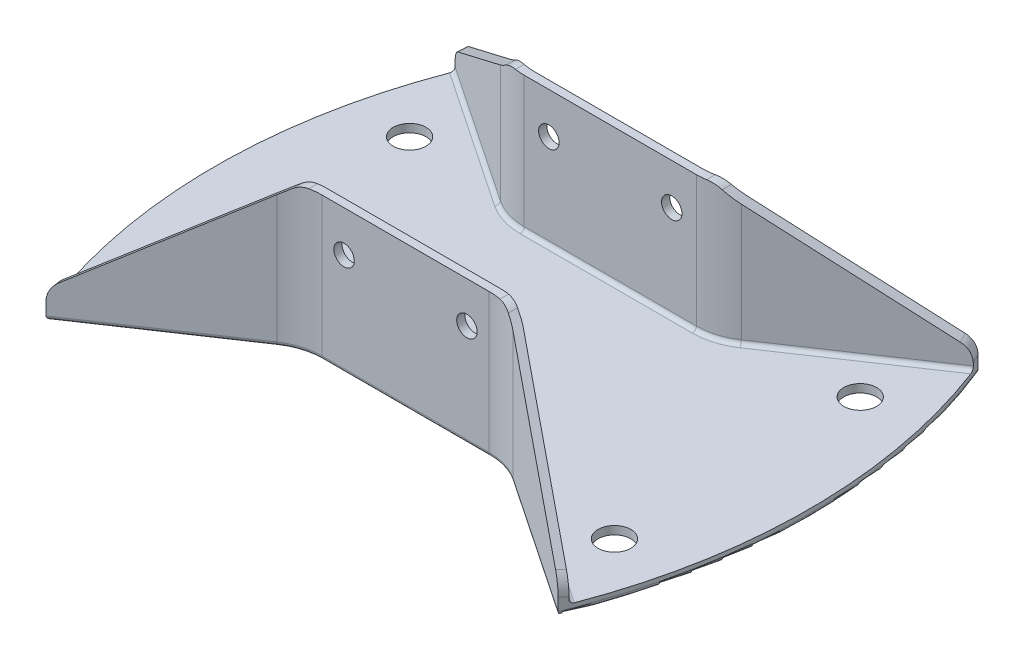
SolidWorks part; units mm, degrees
ref_plane "Front Plane" through (0, 0, 0) normal (0, 0, 1) x (1, 0, 0)
ref_plane "Top Plane" through (0, 0, 0) normal (0, 1, 0) x (1, 0, 0)
ref_plane "Right Plane" through (0, 0, 0) normal (1, 0, 0) x (0, 0, -1)
sketch "Sketch1" plane through (0, 0, 0) normal (0, 1, 0) x (1, 0, 0)
  line L1 (-72.5, 51.25) -> (72.5, 51.25)
  line L2 (-72.5, 51.25) -> (-72.5, -51.25)
  line L3 (-72.5, -51.25) -> (72.5, -51.25)
  line L4 (72.5, 51.25) -> (72.5, -51.25)
  line L5 (-72.5, 51.25) -> (72.5, -51.25) construction
  line L6 (-72.5, -51.25) -> (72.5, 51.25) construction
  point P0 (0, 0)
  dimension "D1" = 145
  dimension "D2" = 102.5
extrude "Boss-Extrude1" add sketch "Sketch1" along normal blind 35
sketch "Sketch2" plane through (0, 35, 0) normal (0, 1, 0) x (1, 0, 0)
  line L0 (-62.5, 51.25) -> (-62.5, -51.25) construction
  line L1 (-25, 26) -> (25, 26)
  line L3 (-25, -26) -> (25, -26)
  line L5 (-25, 26) -> (25, -26) construction
  line L6 (-25, -26) -> (25, 26) construction
  line L7 (72.5, 51.25) -> (-72.5, 51.25) construction
  line L8 (-72.5, -51.25) -> (72.5, -51.25) construction
  line L9 (62.5, 51.25) -> (62.5, -51.25) construction
  line L10 (-72.5, 51.25) -> (-72.5, -51.25) construction
  line L11 (72.5, -51.25) -> (72.5, 51.25) construction
  line L12 (-62.5, 51.25) -> (-25, 26)
  line L13 (62.5, 51.25) -> (25, 26)
  line L14 (-62.5, -51.25) -> (-25, -26)
  line L15 (25, -26) -> (62.5, -51.25)
  arc A0 (-62.5, 51.25) -> (-62.5, -51.25) centre (63.8281, 0) ccw
  arc A1 (62.5, 51.25) -> (62.5, -51.25) centre (-63.8281, 0) cw
  point P0 (0, 0)
  dimension "D1" = 52
  dimension "D2" = 50
  dimension "D3" = 10
  dimension "D4" = 10
  dimension "D5" = 25
  dimension "D6" = 26
extrude "Cut-Extrude1" cut sketch "Sketch2" against normal blind 35 flip side to cut
sketch "Sketch3" plane through (0, 35, 0) normal (0, 1, 0) x (1, 0, 0)
  line L6 (-80, 60.6222) -> (-80, -60.6222)
  line L7 (80, 60.6222) -> (80, -60.6222)
  line L12 (-61.5538, -48.2018) -> (-25.6106, -24)
  line L13 (-25.6106, -24) -> (25.6106, -24)
  line L14 (25.6106, -24) -> (61.5538, -48.2018)
  line L15 (61.5538, 48.2018) -> (25.6106, 24)
  line L16 (25.6106, 24) -> (-25.6106, 24)
  line L17 (-25.6106, 24) -> (-61.5538, 48.2018)
  line L18 (-80, -60.6222) -> (-25.6106, -24)
  line L19 (-25.6106, -24) -> (25.6106, -24)
  line L20 (25.6106, -24) -> (80, -60.6222)
  line L21 (80, 60.6222) -> (25.6106, 24)
  line L22 (25.6106, 24) -> (-25.6106, 24)
  line L23 (-25.6106, 24) -> (-80, 60.6222)
  arc A4 (61.5538, -48.2018) -> (61.5538, 48.2018) centre (-63.8281, 0) ccw
  arc A5 (-61.5538, 48.2018) -> (-61.5538, -48.2018) centre (63.8281, 0) ccw
  dimension "D2" = 80
  dimension "D3" = 80
  dimension "D1" = 2
extrude "Cut-Extrude2" cut sketch "Sketch3" against normal blind 33
sketch "Sketch6" plane through (0, 0, 0) normal (0, 0, 1) x (1, 0, 0)
  line L0 (-65, 5) -> (-25, 35)
  line L1 (-25, 35) -> (25, 35)
  line L2 (25, 35) -> (65, 5)
  line L3 (65, 5) -> (65, 40)
  line L4 (65, 40) -> (-65, 40)
  line L5 (-65, 40) -> (-65, 5)
  circle A0 centre (-15, 25) radius 2.5
  circle A1 centre (15, 25) radius 2.5
  dimension "D7" = 5
  dimension "D8" = 5
  dimension "D1" = 5
  dimension "D2" = 5
  dimension "D3" = 130
  dimension "D4" = 65
  dimension "D5" = 40
  dimension "D6" = 25
  dimension "D9" = 15
  dimension "D10" = 30
extrude "Cut-Extrude6" cut sketch "Sketch6" against normal through all both and the other way through all
fillet "Fillet1" radius 5 8 edges at (62.8812, 6.5891, -50.3001) (62.8812, 6.5891, 50.3001) (25, 35, 25) (25, 35, -25) (-25, 35, -25) (-25, 35, 25) (-62.8812, 6.5891, -50.3001) (-62.8812, 6.5891, 50.3001)
fillet "Fillet3" radius 15 8 edges at (25.6106, 18.2257, 24) (25, 17.357, -26) (25.6106, 18.2257, -24) (25, 17.357, 26) (-25, 17.357, 26) (-25.6106, 18.2257, 24) (-25, 17.357, -26) (-25.6106, 18.2257, -24)
fillet "Fillet2" radius 1 22 edges at (45.6493, 0, 39.9038) (72.5, 0, 0) (45.6493, 0, -39.9038) (0, 0, -26) (-45.6493, 0, -39.9038) (-72.5, 0, 0) (-45.6493, 0, 39.9038) (0, 0, 26) (-46.3322, 2, 37.9525) (0, 2, 24) (46.3322, 2, 37.9525) (46.3322, 2, -37.9525) (0, 2, -24) (-46.3322, 2, -37.9525) (-25.411, 2, 24.6537) (25.411, 2, 24.6537) (25.411, 2, -24.6537) (-25.411, 2, -24.6537) (24.8004, 0, 26.6537) (24.8004, 0, -26.6537) (-24.8004, 0, -26.6537) (-24.8004, 0, 26.6537)
sketch "Sketch7" plane through (0, 2, 0) normal (0, 1, 0) x (1, 0, 0)
  circle A0 centre (55, 30) radius 4
  circle A1 centre (55, -30) radius 4
  circle A2 centre (-55, -30) radius 4
  circle A3 centre (-55, 30) radius 4
  dimension "D1" = 8
  dimension "D2" = 8
  dimension "D3" = 8
  dimension "D4" = 8
  dimension "D5" = 30
  dimension "D6" = 55
  dimension "D7" = 30
  dimension "D8" = 55
extrude "Cut-Extrude8" cut sketch "Sketch7" against normal up to next
